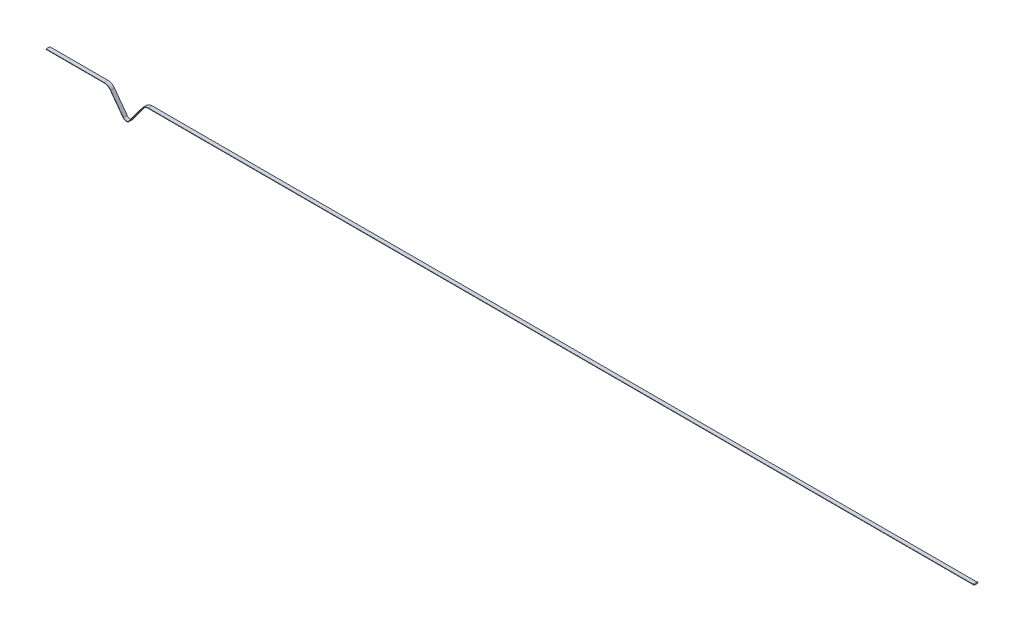
SolidWorks part; units mm, degrees
ref_plane "Front Plane" through (0, 0, 0) normal (0, 0, 1) x (1, 0, 0)
ref_plane "Top Plane" through (0, 0, 0) normal (0, 1, 0) x (1, 0, 0)
ref_plane "Right Plane" through (0, 0, 0) normal (1, 0, 0) x (0, 0, -1)
sketch "Sketch1" plane through (0, 0, 0) normal (1, 0, 0) x (0, 0, -1)
  line L1 (0, 0) -> (6, 0)
  line L2 (0, 0) -> (0, 0.63)
  line L3 (0, 0.63) -> (6, 0.63)
  line L4 (6, 0) -> (6, 0.63)
  dimension "D1" = 0.63
  dimension "D2" = 6
sketch "Sketch2" plane through (0, 0, 0) normal (0, 0, 1) x (1, 0, 0)
  line L0 (0, 0) -> (-1288.0738, 0)
  line L1 (-1297.7064, -4.8779) -> (-1317.7186, -32.1359)
  line L2 (-1327.5689, -32.1359) -> (-1347.5811, -4.8779)
  line L3 (-1357.2138, 0) -> (-1447.8, 0)
  arc A0 (-1288.0738, 0) -> (-1297.7064, -4.8779) centre (-1288.0738, -11.95) ccw
  arc A1 (-1317.7186, -32.1359) -> (-1327.5689, -32.1359) centre (-1322.6438, -28.52) cw
  arc A2 (-1347.5811, -4.8779) -> (-1357.2138, 0) centre (-1357.2138, -11.95) ccw
  circle A3 centre (-1322.6438, -28.52) radius 8 construction
  circle A4 centre (-1288.0738, -11.95) radius 11.95 construction
  circle A5 centre (-1357.2138, -11.95) radius 11.95 construction
  dimension "D1" = 6.11
  dimension "D4" = 1447.8
sweep "Sweep1" add profiles "Sketch1" path "Sketch2"
sketch "Sketch3" plane through (0, 0, 0) normal (0, 0, 1) x (1, 0, 0)
  line L0 (0, 0.63) -> (-1288.0738, 0.63) construction
  line L1 (-1.5, 0.63) -> (-1.5, 0)
  line L2 (0, 0) -> (-1288.0738, 0) construction
  line L3 (-1.5, 0) -> (0, 0)
  line L4 (0, 0) -> (0, 0.63)
  arc A1 (0, 0.63) -> (-1.5, 0.63) centre (-0.75, 0.63) ccw
  dimension "D1" = 0.75
extrude "Boss-Extrude1" add sketch "Sketch3" against normal through all
pattern_curve "CrvPattern1" [suppressed] of bodies 102 driven by "Sketch2" parameters "D1"=2000, "D3"=2, "D2"=1, "D4"=10
